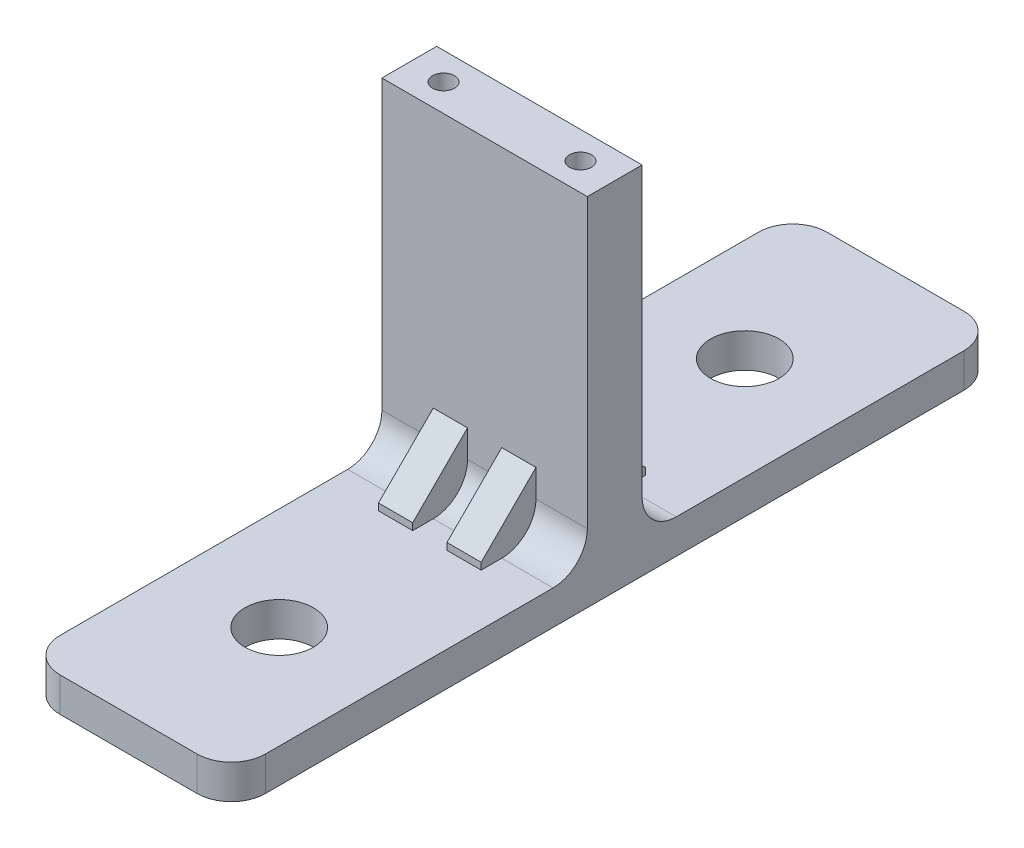
SolidWorks part; units mm, degrees
ref_plane "Front Plane" through (0, 0, 0) normal (0, 0, 1) x (1, 0, 0)
ref_plane "Top Plane" through (0, 0, 0) normal (0, 1, 0) x (1, 0, 0)
ref_plane "Right Plane" through (0, 0, 0) normal (1, 0, 0) x (0, 0, -1)
sketch "Sketch1" plane through (0, 0, 0) normal (1, 0, 0) x (0, 0, -1)
  line L1 (0, 0) -> (60, 0)
  line L2 (0, 0) -> (0, 5)
  line L3 (0, 5) -> (60, 5)
  line L4 (60, 0) -> (60, 5)
  dimension "D1" = 5
  dimension "D2" = 60
extrude "Boss-Extrude1" add sketch "Sketch1" along normal blind 30 contours L3 L4 L1 L2
sketch "Sketch2" plane through (0, 5, 0) normal (0, 1, 0) x (1, 0, 0)
  line L0 (30, 0) -> (30, 60) construction
  line L1 (0, 60) -> (30, 60)
  line L2 (0, 60) -> (0, 52)
  line L3 (0, 52) -> (30, 52)
  line L4 (30, 60) -> (30, 52)
  dimension "D1" = 8
extrude "Boss-Extrude2" add sketch "Sketch2" along normal blind 47
sketch "Sketch3" plane through (0, 5, 0) normal (0, 1, 0) x (1, 0, 0)
  line L0 (30, 0) -> (0, 0) construction
  circle A0 centre (15, 22) radius 5
  point P4 (15, 0)
  dimension "D2" = 10
  dimension "D1" = 22
extrude "Cut-Extrude1" cut sketch "Sketch3" against normal through all
sketch "Sketch5" plane through (0, 52, 0) normal (0, 1, 0) x (1, 0, 0)
  line L0 (0, 60) -> (0, 52) construction
  line L1 (30, 52) -> (30, 60) construction
  circle A0 centre (5, 56) radius 1.6
  circle A1 centre (25, 56) radius 1.6
  point P5 (0, 56)
  dimension "D1" = 3.2
  dimension "D3" = 5
  dimension "D2" = 5
extrude "Cut-Extrude3" cut sketch "Sketch5" against normal blind 14
fillet "Fillet1" radius 5 4 edges at (15, 0, -60) (15, 5, -52) (30, 2.5, 0) (0, 2.5, 0)
ref_plane "Plane1" through (0, 0, -56) normal (0, 0, -1) x (-1, 0, 0)
mirror "Mirror1" about plane through (0, 0, -56) normal (0, 0, -1) of "Boss-Extrude1", "Cut-Extrude1"
fillet "Fillet2" radius 5 3 edges at (15, 5, -60) (0, 2.5, -112) (30, 2.5, -112)
sketch "Sketch6" plane through (0, 5, 0) normal (0, 1, 0) x (1, 0, 0)
  line L0 (0, 52) -> (30, 52) construction
  line L1 (7.5, 52) -> (12.5, 52)
  line L2 (7.5, 52) -> (7.5, 44)
  line L3 (7.5, 44) -> (12.5, 44)
  line L4 (12.5, 52) -> (12.5, 44)
  line L5 (0, 5) -> (0, 47) construction
  line L6 (30, 5) -> (30, 47) construction
  line L7 (17.5, 52) -> (22.5, 52)
  line L8 (17.5, 52) -> (17.5, 44)
  line L9 (17.5, 44) -> (22.5, 44)
  line L10 (22.5, 52) -> (22.5, 44)
  line M5 (30, 47) -> (0, 47)
  dimension "D1" = 5
  dimension "D2" = 8
  dimension "D3" = 7.5
  dimension "D4" = 7.5
extrude "Boss-Extrude3" add sketch "Sketch6" along normal blind 9 contours L10 L7 L8 M5 | L10 L8 L9 M5 | L2 L3 L4 L1 region at (20, 5, -49.5) region at (20, 5, -45.5)
chamfer "Chamfer1" distance 8 angle 45 2 edges at (20, 14, -44) (10, 14, -44)
mirror "Mirror2" about plane through (0, 0, -56) normal (0, 0, -1) of "Chamfer1", "Boss-Extrude3"
